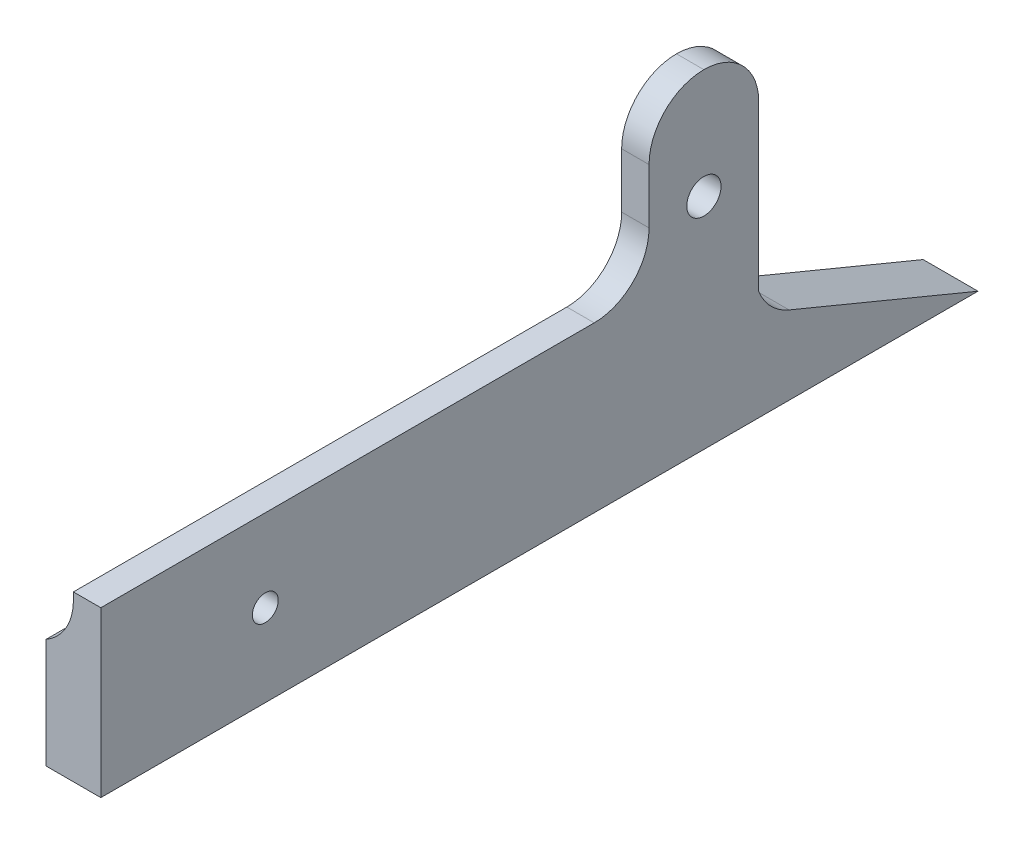
SolidWorks part; units mm, degrees
ref_plane "Front Plane" through (0, 0, 0) normal (0, 0, 1) x (1, 0, 0)
ref_plane "Top Plane" through (0, 0, 0) normal (0, 1, 0) x (1, 0, 0)
ref_plane "Right Plane" through (0, 0, 0) normal (1, 0, 0) x (0, 0, -1)
sketch "Sketch1" plane through (0, 0, 0) normal (1, 0, 0) x (0, 0, -1)
  line L1 (0, 14.692) -> (50.8, -6.35)
  line L2 (50.8, -6.35) -> (-25.4, -6.35)
  line L3 (-25.4, -6.35) -> (-25.4, 6.35)
  line L4 (-25.4, 6.35) -> (-25.4, 19.05)
  line L5 (-25.4, 19.05) -> (0, 19.05)
  line L6 (0, 19.05) -> (0, 14.692)
  dimension "D1" = 76.2
  dimension "D2" = 25.4
  dimension "D3" = 12.7
  dimension "D4" = 6.35
  dimension "D5" = 25.4
  dimension "D6" = 25.4
  dimension "D7" = 22.5
extrude "Boss-Extrude1" add sketch "Sketch1" along normal blind 6.35
fillet "Fillet1" radius 12.7 1 edges at (3.175, 14.692, 0)
sketch "Sketch2" plane through (6.35, 0, 0) normal (1, 0, 0) x (0, 0, -1)
  line L0 (-25.4, -6.35) -> (50.8, -6.35) construction
  line L2 (0, 19.05) -> (0, 69.85)
  line L3 (0, 69.85) -> (-25.4, 69.85)
  line L4 (-25.4, -6.35) -> (-25.4, 69.85)
  line L5 (-25.4, 19.05) -> (-25.4, -6.35) construction
  line L6 (50.8, -6.35) -> (7.0297, 11.7802) construction
  line L7 (-25.4, -6.35) -> (50.8, -6.35)
  line L8 (50.8, -6.35) -> (7.0297, 11.7802)
  arc A0 (0, 19.05) -> (7.0297, 11.7802) centre (11.8898, 23.5135) ccw construction
  arc A1 (0, 19.05) -> (7.0297, 11.7802) centre (11.8898, 23.5135) ccw
  point P6 (-23.5049, -6.35)
  dimension "D1" = 76.2
extrude "Boss-Extrude2" add sketch "Sketch2" along normal blind 6.35
fillet "Fillet2" radius 12.7 1 edges at (6.35, 19.05, 12.7)
sketch "Sketch3" plane through (12.7, 0, 0) normal (1, 0, 0) x (0, 0, -1)
  line L0 (0, 69.85) -> (-25.4, 69.85) construction
  line L1 (-25.4, -6.35) -> (50.8, -6.35) construction
  circle A0 centre (-12.7, 44.45) radius 3.9688
  point P2 (0, 0)
  point P5 (-12.7, 69.85)
  dimension "D1" = 7.9375
  dimension "D2" = 50.8
extrude "Cut-Extrude1" cut sketch "Sketch3" against normal through all both
fillet "Fillet3" radius 12.7 2 edges at (9.525, 69.85, 0) (9.525, 69.85, 25.4)
sketch "Sketch4" plane through (0, 0, 25.4) normal (0, 0, 1) x (1, 0, 0)
  line L6 (6.35, 30.0485) -> (6.35, 31.75)
  line L7 (6.35, 57.15) -> (6.35, 30.0485) construction
  line L8 (6.35, 31.75) -> (12.7, 31.75)
  line L9 (12.7, 57.15) -> (12.7, -6.35) construction
  line L10 (12.7, -6.35) -> (12.7, 57.15)
  line L11 (12.7, 57.15) -> (6.35, 57.15)
  line L12 (6.35, 57.15) -> (6.35, 30.0485)
  line L13 (0, 19.05) -> (0, -6.35)
  line L14 (0, -6.35) -> (12.7, -6.35)
  line L18 (0, 19.05) -> (0, -6.35)
  line L19 (0, -6.35) -> (12.7, -6.35)
  line L20 (12.7, 31.75) -> (12.7, -6.35)
  arc A2 (0, 19.05) -> (6.35, 30.0485) centre (-6.35, 30.0485) ccw
  arc A3 (0, 19.05) -> (6.35, 30.0485) centre (-6.35, 30.0485) ccw
  dimension "D2" = 38.1
  dimension "D1" = 0
extrude "Boss-Extrude3" add sketch "Sketch4" along normal blind 127
fillet "Fillet4" radius 12.7 1 edges at (9.525, 31.75, 25.4)
sketch "Sketch5" plane through (0, 0, 0) normal (-1, 0, 0) x (0, 0, 1)
  line L0 (152.4, -6.35) -> (-50.8, -6.35) construction
  line L1 (152.4, 19.05) -> (152.4, -6.35) construction
  circle A0 centre (114.3, 12.7) radius 3
  dimension "D3" = 6
  dimension "D1" = 19.05
  dimension "D2" = 38.1
extrude "Cut-Extrude2" cut sketch "Sketch5" against normal through all both
